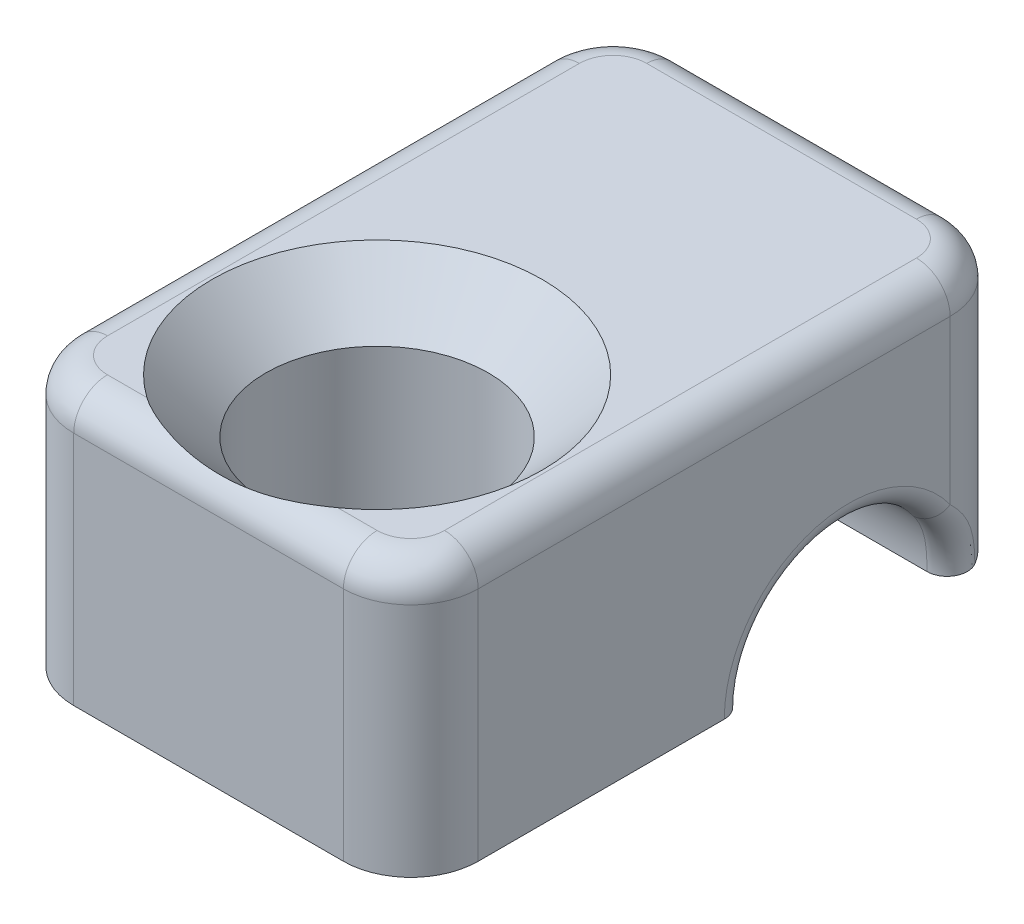
SolidWorks part; units mm, degrees
ref_plane "前基準面" through (0, 0, 0) normal (0, 0, 1) x (1, 0, 0)
ref_plane "上基準面" through (0, 0, 0) normal (0, 1, 0) x (1, 0, 0)
ref_plane "右基準面" through (0, 0, 0) normal (1, 0, 0) x (0, 0, -1)
sketch "草圖1" plane through (0, 0, 0) normal (1, 0, 0) x (0, 0, -1)
  line L0 (0, 0) -> (4.95, 0)
  line L1 (0, 0) -> (0, 4)
  line L2 (0, 4) -> (9, 4)
  line L3 (9, 4) -> (9, 0)
  line L4 (8.05, 0) -> (9, 0)
  arc A0 (8.05, 0) -> (4.95, 0) centre (6.5, 0) ccw
  dimension "D3" = 3.1
  dimension "D1" = 4
  dimension "D2" = 9
  dimension "D4" = 2.5
extrude "填料-伸長1" add sketch "草圖1" along normal blind 6
sketch "草圖2" plane through (0, 0, 0) normal (0, -1, 0) x (-1, 0, 0)
  line L0 (-3, 0) -> (-3, 4.95) construction
  line L1 (-6, 0) -> (0, 0) construction
  line L2 (-6, 4.95) -> (0, 4.95) construction
  circle A0 centre (-3, 2.5) radius 1.65
  dimension "D1" = 3.3
  dimension "D2" = 2.5
extrude "除料-伸長1" cut sketch "草圖2" against normal blind 6
fillet "圓角1" radius 1 4 edges at (6, 2, -9) (0, 2, -9) (6, 2, 0) (0, 2, 0)
chamfer "導角1" distance 0.8 angle 45 1 edges at (3, 4, -4.15)
fillet "圓角2" radius 0.5 8 edges at (0.2929, 4, -8.7071) (3, 4, -9) (5.7071, 4, -8.7071) (6, 4, -4.5) (5.7071, 4, -0.2929) (3, 4, 0) (0.2929, 4, -0.2929) (0, 4, -4.5)
fillet "圓角3" radius 0.3 4 edges at (0, 1.5374, -6.3031) (6, 1.5374, -6.3031)
